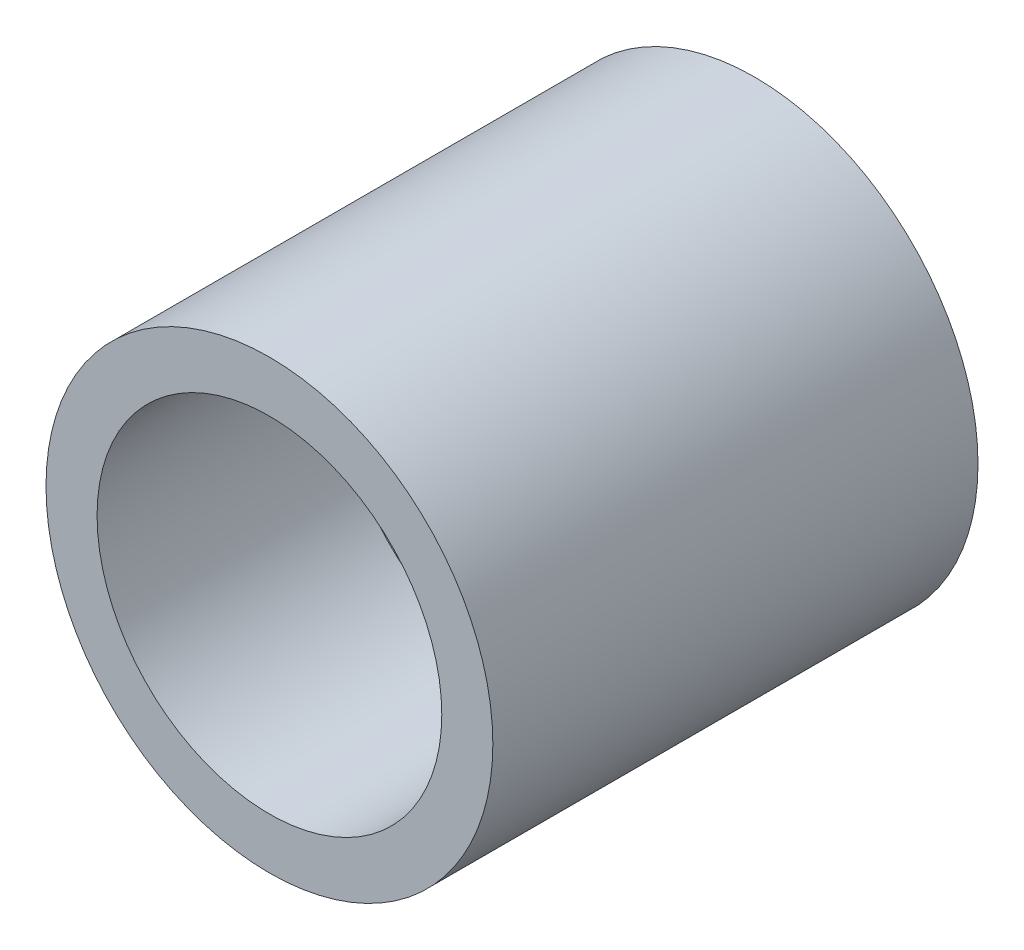
SolidWorks part; units mm, degrees
material "PVC Rigid"
ref_plane "Front Plane" through (0, 0, 0) normal (0, 0, 1) x (1, 0, 0)
ref_plane "Top Plane" through (0, 0, 0) normal (0, 1, 0) x (1, 0, 0)
ref_plane "Right Plane" through (0, 0, 0) normal (1, 0, 0) x (0, 0, -1)
sketch "Sketch1" plane through (0, 0, 0) normal (0, 0, 1) x (1, 0, 0)
  circle A0 centre (0, 0) radius 13.5
  circle A1 centre (0, 0) radius 17.5
  dimension "D1" = 27
  dimension "D2" = 35
sketch3d "3DSketch1"
  line L0 (0, 0, 0) -> (0, 0, -19)
  dimension "D1" = 19
sweep "Sweep1" add profiles "Sketch1" path "3DSketch1"
ref_plane "Plane1" through (0, 0, -19) normal (0, 0, -1) x (-1, 0, 0)
sketch "Sketch2" plane through (0, 0, -19) normal (0, 0, -1) x (-1, 0, 0)
  circle A0 centre (0, 0) radius 17.5
  dimension "D1" = 35
sketch3d "3DSketch2"
  line L0 (0, 0, -19) -> (0, 0, -38)
  line L1 (0, 0, 0) -> (0, 0, -19) construction
  dimension "D1" = 19
sweep "Sweep2" add profiles "Sketch2" path "3DSketch2"
hole_wizard "Pipe Tap Drill for 3/4 Tap1" positions "Sketch4" profile "Sketch3" hole size "3/4" standard "ANSI Inch" end condition up to next
sketch "Sketch4" plane through (0, 0, -38) normal (0, 0, -1) x (-1, 0, 0)
  point P0 (0, 0)
sketch "Sketch3" plane through (0, 0, -38) normal (1, 0, 0) x (0, 1, 0)
  line L0 (0, 0) -> (0, 19)
  line L1 (0, 19) -> (11.5062, 19)
  line L2 (11.5062, 19) -> (11.5062, 0)
  line L5 (11.5062, 0) -> (0, 0)
  line L11 (0, -6.35) -> (0, 107.95) construction
  dimension "Thru Hole Dia." = 23.0124
  dimension "Thru Hole Depth" = 19
